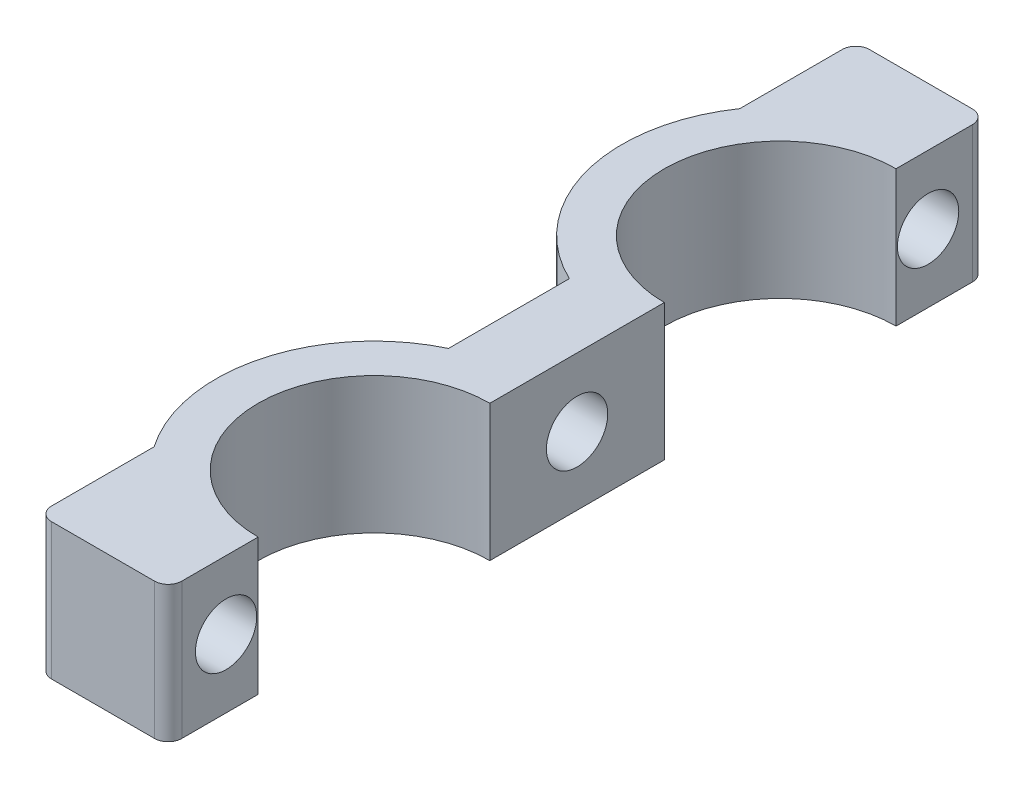
SolidWorks part; units mm, degrees
material "3.1355 (EN-AW 2024)"
ref_plane "Front" through (0, 0, 0) normal (0, 0, 1) x (1, 0, 0)
ref_plane "Top" through (0, 0, 0) normal (0, 1, 0) x (1, 0, 0)
ref_plane "Right" through (0, 0, 0) normal (1, 0, 0) x (0, 0, -1)
sketch "Эскиз1" plane through (0, 0, 0) normal (0, 1, 0) x (1, 0, 0)
  line L0 (0, 0) -> (0, 60) construction
  line L1 (0, 30) -> (-15.0292, 30) construction
  line L2 (0, 0) -> (0, 8)
  line L3 (0, 60) -> (0, 52)
  line L4 (0, 37.8) -> (0, 22.2)
  line L5 (-3, 0) -> (-3, 5.4558)
  line L6 (-3, 35.2558) -> (-3, 24.7442)
  line L7 (-3, 60) -> (-3, 54.5442)
  line L8 (-3, 60) -> (0, 60)
  line L9 (-3, 0) -> (0, 0)
  circle A0 centre (0, 15.1) radius 7.1 construction
  circle A1 centre (0, 44.9) radius 7.1 construction
  arc A2 (0, 8) -> (0, 22.2) centre (0, 15.1) cw
  arc A3 (0, 52) -> (0, 37.8) centre (0, 44.9) ccw
  arc A4 (-3, 5.4558) -> (-3, 24.7442) centre (0, 15.1) cw
  arc A5 (-3, 54.5442) -> (-3, 35.2558) centre (0, 44.9) ccw
  point P9 (0, 22.2)
  dimension "D2" = 15.1
  dimension "D3" = 14.2
  dimension "D1" = 60
  dimension "D4" = 3
extrude "Бобышка-Вытянуть1" add sketch "Эскиз1" along normal blind 10
sketch "Эскиз2" plane through (0, 10, 0) normal (0, 1, 0) x (1, 0, 0)
  line L0 (-3, 60) -> (-8.0498, 60)
  line L1 (-8.0498, 60) -> (-8.0498, 51)
  line L2 (-3, 60) -> (-3, 54.5442)
  line L3 (0, 30) -> (-3, 30) construction
  line L4 (0, 22.2) -> (0, 37.8) construction
  line L5 (-3, 35.2558) -> (-3, 24.7442) construction
  line L6 (-3, 0) -> (-3, 5.4558)
  line L7 (-8.0498, 0) -> (-8.0498, 9)
  line L8 (-3, 0) -> (-8.0498, 0)
  arc A0 (-3, 54.5442) -> (-3, 35.2558) centre (0, 44.9) ccw construction
  arc A1 (-3, 54.5442) -> (-8.0498, 51) centre (0, 44.9) ccw
  arc A2 (-3, 5.4558) -> (-8.0498, 9) centre (0, 15.1) cw
  dimension "D1" = 9
sketch "Эскиз3" plane through (0, 0, 0) normal (-1, 0, 0) x (0, 0, 1)
  line L0 (-60, 5) -> (-54.7288, 5) construction
  line L1 (-60, 10) -> (-60, 0) construction
  line L3 (-30, 10) -> (-30, 0) construction
  line L4 (-35.2558, 10) -> (-24.7442, 10) construction
  line L5 (-35.2558, 0) -> (-24.7442, 0) construction
  circle A0 centre (-55.75, 5) radius 2.25
  circle A1 centre (-4.25, 5) radius 2.25
  point P6 (-58, 5)
  point P7 (-53.5, 5)
  dimension "D1" = 4.5
  dimension "D2" = 2
extrude "Бобышка-Вытянуть2" add sketch "Эскиз2" against normal up to surface (10 mm away) up to face at (-3.8667, 0, -30)
sketch "Эскиз9" plane through (0, 0, 0) normal (0, -1, 0) x (1, 0, 0)
  line L1 (-8.0498, -9) -> (-8.0498, 0) construction
  line L2 (-5, -35.2558) -> (-5, -24.7442)
  line L3 (-5, -34.4329) -> (-5, -25.5671)
  line L4 (-8.0498, 0) -> (-8.0498, -9)
  line L6 (-9.5498, -60) -> (-8.0498, -60)
  line L7 (-3, -35.2558) -> (-3, -24.7442) construction
  line L8 (-3, -35.2558) -> (-3, -24.7442)
  line L9 (-8.0498, -9) -> (-8.0498, 0)
  line L10 (-9.5498, -8.5151) -> (-9.5498, 0)
  line L12 (-9.5498, 0) -> (-8.0498, 0)
  line L13 (-9.5498, -60) -> (-9.5498, -51)
  line L14 (-9.5498, -60) -> (-9.5498, -51.4849)
  line L15 (-8.0498, -60) -> (-8.0498, -51)
  line L16 (-9.5498, -9) -> (-9.5498, 0) construction
  arc A2 (-9.2454, -8.0941) -> (-3.4455, -26.1765) centre (0, -15.1) ccw
  arc A3 (-9.5498, -8.5151) -> (-5, -25.5671) centre (0, -15.1) ccw
  arc A4 (-8.0498, -9) -> (-3, -24.7442) centre (0, -15.1) ccw construction
  arc A5 (-3.4455, -33.8235) -> (-9.2454, -51.9059) centre (0, -44.9) ccw
  arc A6 (-5, -34.4329) -> (-9.5498, -51.4849) centre (0, -44.9) ccw
  arc A7 (-3, -35.2558) -> (-8.0498, -51) centre (0, -44.9) ccw construction
  arc A8 (-8.0498, -9) -> (-3, -24.7442) centre (0, -15.1) ccw
  arc A9 (-3, -35.2558) -> (-8.0498, -51) centre (0, -44.9) ccw
  line M7 (-8.0498, 0) -> (-8.0498, -9)
  arc M9 (-8.0498, -9) -> (-3, -24.7442) centre (0, -15.1) ccw
  line M11 (-3, -24.7442) -> (-3, -35.2558)
  arc M13 (-3, -35.2558) -> (-8.0498, -51) centre (0, -44.9) ccw
  line M15 (-8.0498, -51) -> (-8.0498, -60)
  dimension "D1" = 1.5
  dimension "D2" = 1.5
  dimension "D3" = 2
  dimension "D4" = 1.5
  dimension "D5" = 1.5
extrude "Бобышка-Вытянуть4" add sketch "Эскиз9" against normal through all contours L3 A6 L14 L6 L12 L10 A3 M15 M13 M11 M9 M7 region at (-4.3939, 0, -30)
sketch "Эскиз4" plane through (-5, 0, 0) normal (-1, 0, 0) x (0, 0, 1)
  line L0 (-30, 10) -> (-30, 0) construction
  line L3 (-34.4329, 10) -> (-25.5671, 10) construction
  line L4 (-34.4329, 0) -> (-25.5671, 0) construction
  circle A0 centre (-30, 5) radius 2.25
  dimension "D1" = 4.5
extrude "Вырез-Вытянуть4" cut sketch "Эскиз3" along normal through all
extrude "Вырез-Вытянуть2" cut sketch "Эскиз4" against normal through all
fillet "Скругление2" radius 1 2 edges at (0, 5, 0) (0, 5, -60)
sketch "Эскиз5" plane through (0, 0, 0) normal (0, -1, 0) x (1, 0, 0)
  line L0 (0, -8) -> (0, -8.1)
  line L1 (0, -51.9) -> (0, -52)
  line L2 (0, -37.8) -> (0, -37.9)
  line L3 (0, -22.1) -> (0, -22.2)
  arc A0 (0, -8) -> (0, -22.2) centre (0, -15.1) ccw construction
  arc A1 (0, -37.8) -> (0, -52) centre (0, -44.9) ccw construction
  arc A2 (0, -8) -> (0, -22.2) centre (0, -15.1) ccw
  arc A3 (0, -37.8) -> (0, -52) centre (0, -44.9) ccw
  arc A4 (0, -8.1) -> (0, -22.1) centre (0, -15.1) ccw
  arc A5 (0, -37.9) -> (0, -51.9) centre (0, -44.9) ccw
  dimension "D1" = 0.1
extrude "Бобышка-Вытянуть3" add sketch "Эскиз5" against normal through all
sketch "Эскиз7" plane through (0, 10, 0) normal (0, 1, 0) x (1, 0, 0)
  line L0 (0, 51.9) -> (0, 59) construction
  line L1 (0, 22.1) -> (0, 37.9) construction
  line L2 (0, 1) -> (0, 8.1) construction
  line L3 (0, 51.9) -> (0, 53.4)
  line L4 (0, 22.1) -> (0, 23.6)
  line L5 (0, 6.6) -> (0, 8.1)
  line L6 (0, 36.4) -> (0, 37.9)
  arc A8 (0, 53.4) -> (0, 36.4) centre (0, 44.9) ccw
  arc A9 (0, 53.4) -> (0, 36.4) centre (0, 44.9) ccw
  arc A10 (0, 51.9) -> (0, 37.9) centre (0, 44.9) ccw construction
  arc A11 (0, 23.6) -> (0, 6.6) centre (0, 15.1) ccw
  arc A12 (0, 23.6) -> (0, 6.6) centre (0, 15.1) ccw
  arc A13 (0, 22.1) -> (0, 8.1) centre (0, 15.1) ccw construction
  arc A14 (0, 51.9) -> (0, 37.9) centre (0, 44.9) ccw
  arc A15 (0, 22.1) -> (0, 8.1) centre (0, 15.1) ccw
  dimension "D1" = 1.5
  dimension "D2" = 1.5
extrude "Вырез-Вытянуть3" cut sketch "Эскиз7" against normal through all
fillet "Скругление3" radius 1 2 edges at (-9.5498, 5, 0) (-9.5498, 5, -60)
equation "\"D2@Эскиз1\"=8+\"D3@Эскиз1\"/2"
